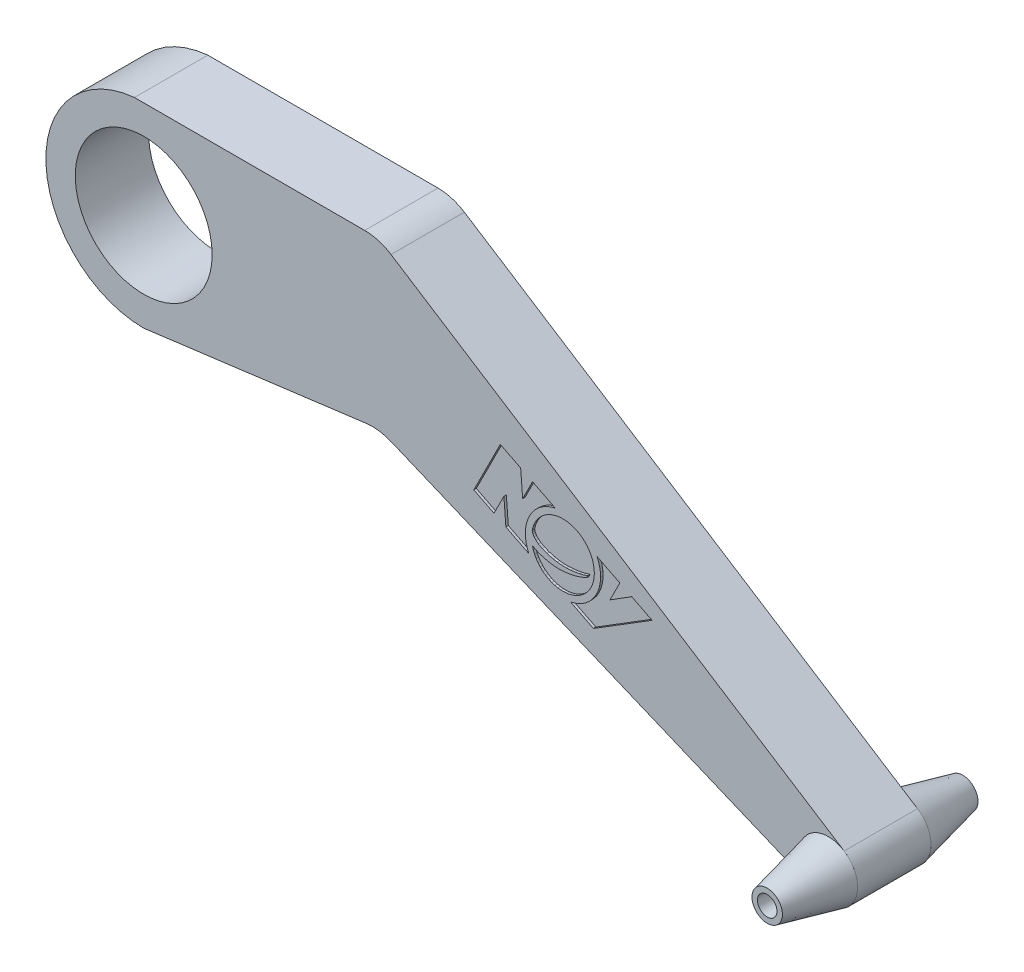
SolidWorks part; units mm, degrees
material "Alumina"
ref_plane "Front Plane" through (0, 0, 0) normal (0, 0, 1) x (1, 0, 0)
ref_plane "Top Plane" through (0, 0, 0) normal (0, 1, 0) x (1, 0, 0)
ref_plane "Right Plane" through (0, 0, 0) normal (1, 0, 0) x (0, 0, -1)
sketch "Sketch1" plane through (0, 0, 0) normal (0, 0, 1) x (1, 0, 0)
  line L1 (-1.8889, 19.9106) -> (45.1848, 19.9106)
  line L5 (50.5757, 18.3331) -> (143.2345, -40.9737)
  line L7 (48.1111, 31.6525) -> (48.1111, -43.2848) construction
  line L10 (140, -52.0272) -> (50.5846, -14.7897)
  line L11 (0, -20) -> (45.4538, -14.1042)
  line L13 (140, -0.7629) -> (140, -46.0272) construction
  circle A0 centre (0, 0) radius 14
  arc A1 (-1.8889, 19.9106) -> (0, -20) centre (0, 0) ccw
  arc A8 (143.2345, -40.9737) -> (140, -52.0272) centre (140, -46.0272) cw
  circle A9 centre (140, -46.0272) radius 2
  arc A11 (50.5757, 18.3331) -> (45.1848, 19.9106) centre (45.1848, 9.9106) ccw
  arc A12 (50.5846, -14.7897) -> (45.4538, -14.1042) centre (46.7401, -24.0212) ccw
  point P12 (48.1111, -13.7596)
  point P20 (48.1111, 19.9106)
  point P22 (140, -46.0272)
  dimension "D1" = 28
  dimension "D2" = 20
  dimension "D3" = 50
  dimension "D4" = 4
  dimension "D6" = 140
  dimension "D7" = 150
  dimension "D5" = 10
  dimension "D9" = 34.0148
  dimension "D8" = 6
  dimension "D10" = 45.4538
  dimension "D11" = 10
extrude "Boss-Extrude1" add sketch "Sketch1" along normal mid plane 15
sketch "Sketch2" plane through (0, 0, 7.5) normal (0, 0, 1) x (1, 0, 0)
  line L0 (0, 0) -> (30.9788, 0) construction
  line L1 (50, 0) -> (-50, 0) construction
  line L2 (15.4894, -1.5) -> (15.4894, 1.5)
  line L3 (15.4894, 1.5) -> (13.9194, 1.5)
  line L4 (15.4894, -1.5) -> (13.9194, -1.5)
  circle A0 centre (0, 0) radius 14 construction
  arc A1 (13.9194, -1.5) -> (13.9194, 1.5) centre (0, 0) ccw
  point P10 (15.4894, 0)
  dimension "D1" = 1.57
  dimension "D2" = 3
extrude "Cut-Extrude1" [suppressed] cut sketch "Sketch2" against normal mid plane 33.14
sketch "Sketch3" [suppressed] plane through (0, 0, 7.5) normal (0, 0, 1) x (1, 0, 0)
  line L0 (0, 33) -> (0, -33) construction
  line L1 (0, -50) -> (0, 50) construction
  line L2 (-6.5, 33) -> (6.5, 33)
  line L3 (6.5, 33) -> (6.5, -33)
  line L4 (6.5, -33) -> (-6.5, -33)
  line L5 (-6.5, -33) -> (-6.5, 33)
  point P10 (0, 33)
  dimension "D1" = 33
  dimension "D2" = 13
  dimension "D3" = 33
extrude "Boss-Extrude2" [suppressed] add sketch "Sketch3" against normal blind 15
sketch "Sketch4" [suppressed] plane through (0, 0, 7.5) normal (0, 0, 1) x (1, 0, 0)
  line L0 (0, 33) -> (0, -33) construction
  line L1 (6.5, 33) -> (-6.5, 33) construction
  line L2 (-6.5, -33) -> (6.5, -33) construction
  line L3 (-7.9109, 0) -> (7.7913, 0) construction
  line L4 (50, 0) -> (-50, 0) construction
  circle A0 centre (0, 0) radius 14
  circle A1 centre (0, 25.4313) radius 4
  circle A2 centre (0, -25.4313) radius 4
  dimension "D1" = 28
  dimension "D2" = 8
  dimension "D3" = 25.4313
extrude "Cut-Extrude2" [suppressed] cut sketch "Sketch4" against normal blind 15
fillet "Fillet1" [suppressed] radius 4
ref_plane "Plane2" through (0, 0, -7.5) normal (0, 0, -1) x (-1, 0, 0)
sketch "Sketch5" plane through (0, 0, -7.5) normal (0, 0, -1) x (-1, 0, 0)
  circle A0 centre (-140, -46.0272) radius 6
extrude "Boss-Extrude3" add sketch "Sketch5" along normal blind 12.5 draft 13 separate body contours A0
sketch "Sketch6" plane through (0, 0, -20) normal (0, 0, -1) x (-1, 0, 0)
  circle A0 centre (-140, -46.0272) radius 2
extrude "Cut-Extrude3" cut sketch "Sketch6" against normal blind 12.5 contours A0
ref_plane "Plane3" through (0, 0, 7.5) normal (0, 0, -1) x (-1, 0, 0)
mirror "Mirror4" about plane through (0, 0, 0) normal (0, 0, 1) of bodies 106
ref_plane "Plane4" through (0, 0, -7.5) normal (0, 0, -1) x (-1, 0, 0)
sketch "Sketch8" plane through (0, 0, -7.5) normal (0, 0, -1) x (-1, 0, 0)
  line L0 (-79.551, -14.2243) -> (-79.2828, -14.8235)
  line L1 (-79.2828, -14.8235) -> (-79.0804, -15.4349)
  line L2 (-79.0804, -15.4349) -> (-78.9422, -16.0541)
  line L3 (-78.9422, -16.0541) -> (-78.8669, -16.6769)
  line L4 (-78.8669, -16.6769) -> (-78.853, -17.299)
  line L5 (-78.853, -17.299) -> (-78.8992, -17.9158)
  line L6 (-78.8992, -17.9158) -> (-79.004, -18.5233)
  line L7 (-79.004, -18.5233) -> (-79.1661, -19.1169)
  line L8 (-79.1661, -19.1169) -> (-79.3839, -19.6924)
  line L9 (-79.3839, -19.6924) -> (-79.6562, -20.2454)
  line L10 (-79.6562, -20.2454) -> (-79.9815, -20.7716)
  line L11 (-79.9815, -20.7716) -> (-80.3583, -21.2667)
  line L12 (-80.3583, -21.2667) -> (-80.7854, -21.7263)
  line L13 (-80.7854, -21.7263) -> (-81.2612, -22.1461)
  line L14 (-81.2612, -22.1461) -> (-81.7843, -22.5217)
  line L15 (-81.7843, -22.5217) -> (-82.3534, -22.8488)
  line L16 (-82.3534, -22.8488) -> (-83.0249, -23.1445)
  line L17 (-83.0249, -23.1445) -> (-83.7111, -23.3581)
  line L18 (-83.7111, -23.3581) -> (-84.4058, -23.4916)
  line L19 (-84.4058, -23.4916) -> (-85.103, -23.547)
  line L20 (-85.103, -23.547) -> (-85.7966, -23.5262)
  line L21 (-85.7966, -23.5262) -> (-86.4805, -23.4313)
  line L22 (-86.4805, -23.4313) -> (-87.1486, -23.2642)
  line L23 (-87.1486, -23.2642) -> (-87.7949, -23.027)
  line L24 (-87.7949, -23.027) -> (-87.1299, -22.7307)
  line L25 (-87.1299, -22.7307) -> (-86.3728, -22.2754)
  line L26 (-86.3728, -22.2754) -> (-85.5204, -21.6356)
  line L27 (-85.5204, -21.6356) -> (-84.5695, -20.7858)
  line L28 (-84.5695, -20.7858) -> (-83.8725, -20.0409)
  line L29 (-83.8725, -20.0409) -> (-83.2548, -19.2361)
  line L30 (-83.2548, -19.2361) -> (-82.7149, -18.3881)
  line L31 (-82.7149, -18.3881) -> (-82.2513, -17.5137)
  line L32 (-82.2513, -17.5137) -> (-81.8625, -16.6296)
  line L33 (-81.8625, -16.6296) -> (-81.5469, -15.7526)
  line L34 (-81.5469, -15.7526) -> (-81.303, -14.8993)
  line L35 (-81.303, -14.8993) -> (-81.1292, -14.0865)
  line L36 (-81.1292, -14.0865) -> (-81.3655, -13.7762)
  line L37 (-81.3655, -13.7762) -> (-81.6354, -14.5442)
  line L38 (-81.6354, -14.5442) -> (-81.967, -15.3373)
  line L39 (-81.967, -15.3373) -> (-82.3578, -16.1402)
  line L40 (-82.3578, -16.1402) -> (-82.8049, -16.9373)
  line L41 (-82.8049, -16.9373) -> (-83.3057, -17.713)
  line L42 (-83.3057, -17.713) -> (-83.8576, -18.4519)
  line L43 (-83.8576, -18.4519) -> (-84.4578, -19.1384)
  line L44 (-84.4578, -19.1384) -> (-85.1037, -19.757)
  line L45 (-85.1037, -19.757) -> (-86.1224, -20.5643)
  line L46 (-86.1224, -20.5643) -> (-87.0136, -21.1285)
  line L47 (-87.0136, -21.1285) -> (-87.7822, -21.4864)
  line L48 (-87.7822, -21.4864) -> (-88.4331, -21.6753)
  line L49 (-88.4331, -21.6753) -> (-88.9714, -21.732)
  line L50 (-88.9714, -21.732) -> (-89.4021, -21.6936)
  line L51 (-89.4021, -21.6936) -> (-89.73, -21.5971)
  line L52 (-89.73, -21.5971) -> (-89.9601, -21.4797)
  line L53 (-89.9601, -21.4797) -> (-90.0224, -21.4349)
  line L54 (-90.0224, -21.4349) -> (-90.5407, -20.7802)
  line L55 (-90.5407, -20.7802) -> (-90.9783, -20.0468)
  line L56 (-90.9783, -20.0468) -> (-91.2464, -19.4476)
  line L57 (-91.2464, -19.4476) -> (-91.4489, -18.8361)
  line L58 (-91.4489, -18.8361) -> (-91.5871, -18.2168)
  line L59 (-91.5871, -18.2168) -> (-91.6625, -17.5939)
  line L60 (-91.6625, -17.5939) -> (-91.6764, -16.9719)
  line L61 (-91.6764, -16.9719) -> (-91.6302, -16.355)
  line L62 (-91.6302, -16.355) -> (-91.5254, -15.7475)
  line L63 (-91.5254, -15.7475) -> (-91.3634, -15.1539)
  line L64 (-91.3634, -15.1539) -> (-91.1455, -14.5784)
  line L65 (-91.1455, -14.5784) -> (-90.8733, -14.0253)
  line L66 (-90.8733, -14.0253) -> (-90.548, -13.4991)
  line L67 (-90.548, -13.4991) -> (-90.1711, -13.004)
  line L68 (-90.1711, -13.004) -> (-89.7441, -12.5444)
  line L69 (-89.7441, -12.5444) -> (-89.2682, -12.1246)
  line L70 (-89.2682, -12.1246) -> (-88.745, -11.7489)
  line L71 (-88.745, -11.7489) -> (-88.1758, -11.4218)
  line L72 (-88.1758, -11.4218) -> (-87.5766, -11.1536)
  line L73 (-87.5766, -11.1536) -> (-86.9653, -10.9512)
  line L74 (-86.9653, -10.9512) -> (-86.346, -10.813)
  line L75 (-86.346, -10.813) -> (-85.7232, -10.7376)
  line L76 (-85.7232, -10.7376) -> (-85.1011, -10.7238)
  line L77 (-85.1011, -10.7238) -> (-84.4842, -10.7699)
  line L78 (-84.4842, -10.7699) -> (-83.8768, -10.8747)
  line L79 (-83.8768, -10.8747) -> (-83.2831, -11.0368)
  line L80 (-83.2831, -11.0368) -> (-82.7076, -11.2546)
  line L81 (-82.7076, -11.2546) -> (-82.1546, -11.5269)
  line L82 (-82.1546, -11.5269) -> (-81.6283, -11.8521)
  line L83 (-81.6283, -11.8521) -> (-81.1332, -12.229)
  line L84 (-81.1332, -12.229) -> (-80.6736, -12.6561)
  line L85 (-80.6736, -12.6561) -> (-80.2538, -13.1319)
  line L86 (-80.2538, -13.1319) -> (-79.8781, -13.6551)
  line L87 (-79.8781, -13.6551) -> (-79.551, -14.2243)
  line L88 (-76.6715, -6.0002) -> (-77.0514, -11.2288)
  line L89 (-77.0514, -11.2288) -> (-79.0881, -7.2315)
  line L90 (-79.0881, -7.2315) -> (-83.73, -9.5967)
  line L91 (-83.73, -9.5967) -> (-82.9103, -9.8114)
  line L92 (-82.9103, -9.8114) -> (-82.1189, -10.1143)
  line L93 (-82.1189, -10.1143) -> (-81.3639, -10.5028)
  line L94 (-81.3639, -10.5028) -> (-80.653, -10.9744)
  line L95 (-80.653, -10.9744) -> (-79.9941, -11.5266)
  line L96 (-79.9941, -11.5266) -> (-79.3951, -12.157)
  line L97 (-79.3951, -12.157) -> (-78.8639, -12.863)
  line L98 (-78.8639, -12.863) -> (-78.4083, -13.6421)
  line L99 (-78.4083, -13.6421) -> (-78.0458, -14.4685)
  line L100 (-78.0458, -14.4685) -> (-77.787, -15.3132)
  line L101 (-77.787, -15.3132) -> (-77.6291, -16.1682)
  line L102 (-77.6291, -16.1682) -> (-77.5696, -17.0258)
  line L103 (-77.5696, -17.0258) -> (-77.6059, -17.8781)
  line L104 (-77.6059, -17.8781) -> (-77.7354, -18.7173)
  line L105 (-77.7354, -18.7173) -> (-77.9556, -19.5354)
  line L106 (-77.9556, -19.5354) -> (-78.2637, -20.3248)
  line L107 (-78.2637, -20.3248) -> (-73.6039, -17.9505)
  line L108 (-73.6039, -17.9505) -> (-72.5101, -3.8799)
  line L109 (-72.5101, -3.8799) -> (-76.6715, -6.0002)
  line L110 (-86.7991, -24.6739) -> (-91.4762, -27.0569)
  line L111 (-91.4762, -27.0569) -> (-95.9297, -24.2911)
  line L112 (-95.9297, -24.2911) -> (-93.893, -28.2884)
  line L113 (-93.893, -28.2884) -> (-98.0097, -30.3859)
  line L114 (-98.0097, -30.3859) -> (-103.476, -19.6578)
  line L115 (-103.476, -19.6578) -> (-99.3243, -17.5424)
  line L116 (-99.3243, -17.5424) -> (-94.8707, -20.3081)
  line L117 (-94.8707, -20.3081) -> (-96.9074, -16.3109)
  line L118 (-96.9074, -16.3109) -> (-92.2653, -13.9456)
  line L119 (-92.2653, -13.9456) -> (-92.5734, -14.735)
  line L120 (-92.5734, -14.735) -> (-92.7935, -15.5533)
  line L121 (-92.7935, -15.5533) -> (-92.9231, -16.3925)
  line L122 (-92.9231, -16.3925) -> (-92.9594, -17.2448)
  line L123 (-92.9594, -17.2448) -> (-92.8999, -18.1025)
  line L124 (-92.8999, -18.1025) -> (-92.742, -18.9576)
  line L125 (-92.742, -18.9576) -> (-92.4831, -19.8023)
  line L126 (-92.4831, -19.8023) -> (-92.1206, -20.6289)
  line L127 (-92.1206, -20.6289) -> (-91.6651, -21.4079)
  line L128 (-91.6651, -21.4079) -> (-91.1339, -22.1138)
  line L129 (-91.1339, -22.1138) -> (-90.5349, -22.7441)
  line L130 (-90.5349, -22.7441) -> (-89.8761, -23.2963)
  line L131 (-89.8761, -23.2963) -> (-89.1652, -23.7678)
  line L132 (-89.1652, -23.7678) -> (-88.4102, -24.1563)
  line L133 (-88.4102, -24.1563) -> (-87.6189, -24.4591)
  line L134 (-87.6189, -24.4591) -> (-86.7991, -24.6739)
extrude "Cut-Extrude4" cut sketch "Sketch8" against normal blind 0.5
sketch "Sketch10" plane through (0, 0, 7.5) normal (0, 0, -1) x (-1, 0, 0)
  line L0 (-90.1816, -7.0169) -> (-80.0322, -27.0533)
  line L1 (-143.2345, -40.9737) -> (-50.5757, 18.3331) construction
  line L2 (-50.5846, -14.7897) -> (-140, -52.0272) construction
  line L7 (-50.5757, 18.3331) -> (-143.2345, -40.9737)
  line L8 (1.8889, 19.9106) -> (-45.1848, 19.9106)
  line L9 (-45.4538, -14.1042) -> (0, -20)
  line L10 (-140, -52.0272) -> (-50.5846, -14.7897)
  line L11 (-50.5757, 18.3331) -> (-90.1816, -7.0169)
  line L12 (1.8889, 19.9106) -> (-45.1848, 19.9106)
  line L13 (-45.4538, -14.1042) -> (0, -20)
  line L14 (-80.0322, -27.0533) -> (-50.5846, -14.7897)
  arc A4 (-143.2345, -40.9737) -> (-140, -52.0272) centre (-140, -46.0272) ccw
  arc A5 (-45.1848, 19.9106) -> (-50.5757, 18.3331) centre (-45.1848, 9.9106) ccw
  arc A6 (0, -20) -> (1.8889, 19.9106) centre (0, 0) ccw
  arc A7 (-45.4538, -14.1042) -> (-50.5846, -14.7897) centre (-46.7401, -24.0212) ccw
  arc A9 (-45.1848, 19.9106) -> (-50.5757, 18.3331) centre (-45.1848, 9.9106) ccw
  arc A10 (0, -20) -> (1.8889, 19.9106) centre (0, 0) ccw
  arc A11 (-45.4538, -14.1042) -> (-50.5846, -14.7897) centre (-46.7401, -24.0212) ccw
  dimension "D1" = 0
ref_axis "Axis1" through (90.1816, -7.0169, 7.5) along (-0.4519, -0.8921, 0)
ref_plane "Plane5" through (74.5954, -37.7862, 0) normal (-0.8921, 0.4519, 0) x (-0.4519, -0.8921, 0)
ref_plane "Plane6" through (0, 0, 8.5) normal (0, 0, -1) x (-1, 0, 0)
sketch "Sketch15" plane through (0, 0, 8.5) normal (0, 0, -1) x (-1, 0, 0)
  line L136 (-78.4365, -19.7446) -> (-78.7484, -20.5325)
  line L137 (-78.2126, -18.9274) -> (-78.4365, -19.7446)
  line L138 (-78.0791, -18.0889) -> (-78.2126, -18.9274)
  line L139 (-78.0387, -17.2368) -> (-78.0791, -18.0889)
  line L140 (-78.0941, -16.379) -> (-78.0387, -17.2368)
  line L141 (-78.248, -15.5232) -> (-78.0941, -16.379)
  line L142 (-78.5028, -14.6773) -> (-78.248, -15.5232)
  line L143 (-78.8613, -13.8492) -> (-78.5028, -14.6773)
  line L144 (-79.3133, -13.0679) -> (-78.8613, -13.8492)
  line L145 (-79.8412, -12.3594) -> (-79.3133, -13.0679)
  line L146 (-80.4372, -11.7262) -> (-79.8412, -12.3594)
  line L147 (-81.0934, -11.1709) -> (-80.4372, -11.7262)
  line L148 (-81.8021, -10.6959) -> (-81.0934, -11.1709)
  line L149 (-82.5553, -10.3039) -> (-81.8021, -10.6959)
  line L150 (-83.3452, -9.9973) -> (-82.5553, -10.3039)
  line L151 (-84.164, -9.7787) -> (-83.3452, -9.9973)
  line L152 (-79.5107, -7.4354) -> (-84.164, -9.7787)
  line L153 (-77.493, -11.4422) -> (-79.5107, -7.4354)
  line L154 (-77.088, -6.2154) -> (-77.493, -11.4422)
  line L155 (-72.9264, -4.1197) -> (-77.088, -6.2154)
  line L156 (-67.511, -14.8736) -> (-72.9264, -4.1197)
  line L157 (-71.6375, -16.9516) -> (-67.511, -14.8736)
  line L158 (-73.6552, -12.9448) -> (-71.6375, -16.9516)
  line L159 (-74.0601, -18.1716) -> (-73.6552, -12.9448)
  line L160 (-78.7484, -20.5325) -> (-74.0601, -18.1716)
  line L161 (-103.9666, -19.7509) -> (-99.7952, -17.6503)
  line L162 (-91.9753, -27.1933) -> (-103.9666, -19.7509)
  line L163 (-87.3044, -24.8411) -> (-91.9753, -27.1933)
  line L164 (-88.1231, -24.6225) -> (-87.3044, -24.8411)
  line L165 (-88.9129, -24.316) -> (-88.1231, -24.6225)
  line L166 (-89.6661, -23.9239) -> (-88.9129, -24.316)
  line L167 (-90.3747, -23.449) -> (-89.6661, -23.9239)
  line L168 (-91.0309, -22.8937) -> (-90.3747, -23.449)
  line L169 (-91.6269, -22.2606) -> (-91.0309, -22.8937)
  line L170 (-92.1547, -21.5521) -> (-91.6269, -22.2606)
  line L171 (-92.6066, -20.771) -> (-92.1547, -21.5521)
  line L172 (-92.9652, -19.9428) -> (-92.6066, -20.771)
  line L173 (-93.2201, -19.0968) -> (-92.9652, -19.9428)
  line L174 (-93.3739, -18.2409) -> (-93.2201, -19.0968)
  line L175 (-93.4294, -17.383) -> (-93.3739, -18.2409)
  line L176 (-93.389, -16.5309) -> (-93.4294, -17.383)
  line L177 (-93.2555, -15.6923) -> (-93.389, -16.5309)
  line L178 (-93.0316, -14.8751) -> (-93.2555, -15.6923)
  line L179 (-92.7197, -14.0872) -> (-93.0316, -14.8751)
  line L180 (-97.3727, -16.4304) -> (-92.7197, -14.0872)
  line L181 (-95.355, -20.4372) -> (-97.3727, -16.4304)
  line L182 (-99.7952, -17.6503) -> (-95.355, -20.4372)
  line L183 (-91.7265, -19.5937) -> (-91.4612, -20.1942)
  line L184 (-91.9261, -18.9813) -> (-91.7265, -19.5937)
  line L185 (-92.0614, -18.3613) -> (-91.9261, -18.9813)
  line L186 (-92.1338, -17.7381) -> (-92.0614, -18.3613)
  line L187 (-92.1447, -17.116) -> (-92.1338, -17.7381)
  line L188 (-92.0956, -16.4993) -> (-92.1447, -17.116)
  line L189 (-91.9879, -15.8923) -> (-92.0956, -16.4993)
  line L190 (-91.8231, -15.2994) -> (-91.9879, -15.8923)
  line L191 (-91.6025, -14.725) -> (-91.8231, -15.2994)
  line L192 (-91.3276, -14.1732) -> (-91.6025, -14.725)
  line L193 (-90.9999, -13.6485) -> (-91.3276, -14.1732)
  line L194 (-90.6207, -13.1553) -> (-90.9999, -13.6485)
  line L195 (-90.1915, -12.6977) -> (-90.6207, -13.1553)
  line L196 (-89.7137, -12.2802) -> (-90.1915, -12.6977)
  line L197 (-89.1888, -11.907) -> (-89.7137, -12.2802)
  line L198 (-88.6181, -11.5826) -> (-89.1888, -11.907)
  line L199 (-88.0176, -11.3173) -> (-88.6181, -11.5826)
  line L200 (-87.4052, -11.1177) -> (-88.0176, -11.3173)
  line L201 (-86.7853, -10.9824) -> (-87.4052, -11.1177)
  line L202 (-86.1621, -10.91) -> (-86.7853, -10.9824)
  line L203 (-85.54, -10.899) -> (-86.1621, -10.91)
  line L204 (-84.9233, -10.9481) -> (-85.54, -10.899)
  line L205 (-84.3163, -11.0558) -> (-84.9233, -10.9481)
  line L206 (-83.7234, -11.2206) -> (-84.3163, -11.0558)
  line L207 (-83.149, -11.4412) -> (-83.7234, -11.2206)
  line L208 (-82.5972, -11.7161) -> (-83.149, -11.4412)
  line L209 (-82.0725, -12.0438) -> (-82.5972, -11.7161)
  line L210 (-81.5792, -12.423) -> (-82.0725, -12.0438)
  line L211 (-81.1217, -12.8523) -> (-81.5792, -12.423)
  line L212 (-80.7041, -13.3301) -> (-81.1217, -12.8523)
  line L213 (-80.3309, -13.8551) -> (-80.7041, -13.3301)
  line L214 (-80.0065, -14.4258) -> (-80.3309, -13.8551)
  line L215 (-79.674, -15.2125) -> (-80.0065, -14.4258)
  line L216 (-79.4528, -16.0176) -> (-79.674, -15.2125)
  line L217 (-79.4536, -16.0943) -> (-79.4528, -16.0176)
  line L218 (-79.495, -16.3494) -> (-79.4536, -16.0943)
  line L219 (-79.6113, -16.6708) -> (-79.495, -16.3494)
  line L220 (-79.8351, -17.0407) -> (-79.6113, -16.6708)
  line L221 (-80.1993, -17.4412) -> (-79.8351, -17.0407)
  line L222 (-80.7366, -17.8543) -> (-80.1993, -17.4412)
  line L223 (-81.4799, -18.2622) -> (-80.7366, -17.8543)
  line L224 (-82.4619, -18.6469) -> (-81.4799, -18.2622)
  line L225 (-83.7155, -18.9906) -> (-82.4619, -18.6469)
  line L226 (-84.5964, -19.1454) -> (-83.7155, -18.9906)
  line L227 (-85.505, -19.2232) -> (-84.5964, -19.1454)
  line L228 (-86.4272, -19.231) -> (-85.505, -19.2232)
  line L229 (-87.3489, -19.1758) -> (-86.4272, -19.231)
  line L230 (-88.256, -19.0647) -> (-87.3489, -19.1758)
  line L231 (-89.1345, -18.9047) -> (-88.256, -19.0647)
  line L232 (-89.9701, -18.7029) -> (-89.1345, -18.9047)
  line L233 (-90.7489, -18.4661) -> (-89.9701, -18.7029)
  line L234 (-90.6386, -18.8403) -> (-90.7489, -18.4661)
  line L235 (-89.8805, -19.181) -> (-90.6386, -18.8403)
  line L236 (-89.0483, -19.4891) -> (-89.8805, -19.181)
  line L237 (-88.1544, -19.7535) -> (-89.0483, -19.4891)
  line L238 (-87.2116, -19.9631) -> (-88.1544, -19.7535)
  line L239 (-86.2324, -20.1067) -> (-87.2116, -19.9631)
  line L240 (-85.2293, -20.1731) -> (-86.2324, -20.1067)
  line L241 (-84.2151, -20.1512) -> (-85.2293, -20.1731)
  line L242 (-83.2021, -20.0299) -> (-84.2151, -20.1512)
  line L243 (-81.9545, -19.766) -> (-83.2021, -20.0299)
  line L244 (-80.9343, -19.4573) -> (-81.9545, -19.766)
  line L245 (-80.1193, -19.1163) -> (-80.9343, -19.4573)
  line L246 (-79.4871, -18.7554) -> (-80.1193, -19.1163)
  line L247 (-79.6782, -19.4168) -> (-79.4871, -18.7554)
  line L248 (-79.9387, -20.0543) -> (-79.6782, -19.4168)
  line L249 (-80.2668, -20.6619) -> (-79.9387, -20.0543)
  line L250 (-80.6604, -21.2333) -> (-80.2668, -20.6619)
  line L251 (-81.1175, -21.7627) -> (-80.6604, -21.2333)
  line L252 (-81.6361, -22.2438) -> (-81.1175, -21.7627)
  line L253 (-82.2142, -22.6706) -> (-81.6361, -22.2438)
  line L254 (-82.8499, -23.0371) -> (-82.2142, -22.6706)
  line L255 (-83.4503, -23.3024) -> (-82.8499, -23.0371)
  line L256 (-84.0627, -23.5019) -> (-83.4503, -23.3024)
  line L257 (-84.6826, -23.6372) -> (-84.0627, -23.5019)
  line L258 (-85.3058, -23.7096) -> (-84.6826, -23.6372)
  line L259 (-85.9278, -23.7205) -> (-85.3058, -23.7096)
  line L260 (-86.5445, -23.6715) -> (-85.9278, -23.7205)
  line L261 (-87.1515, -23.5638) -> (-86.5445, -23.6715)
  line L262 (-87.7443, -23.399) -> (-87.1515, -23.5638)
  line L263 (-88.3188, -23.1784) -> (-87.7443, -23.399)
  line L264 (-88.8705, -22.9036) -> (-88.3188, -23.1784)
  line L265 (-89.3952, -22.5759) -> (-88.8705, -22.9036)
  line L266 (-89.8885, -22.1967) -> (-89.3952, -22.5759)
  line L267 (-90.3461, -21.7675) -> (-89.8885, -22.1967)
  line L268 (-90.7636, -21.2897) -> (-90.3461, -21.7675)
  line L269 (-91.1367, -20.7648) -> (-90.7636, -21.2897)
  line L270 (-91.4612, -20.1942) -> (-91.1367, -20.7648)
extrude "Cut-Extrude9" cut sketch "Sketch15" along normal blind 0.5 from surface contours L136 L160 L159 L158 L157 L156 L155 L154 L153 L152 L151 L150 L149 L148 L147 L146 L145 L144 L143 L142 L141 L140 L139 L138 L137 | L183 L270 L269 L268 L267 L266 L265 L264 L263 L262 L261 L260 L259 L258 L257 L256 L255 L254 L253 L252 L251 L250 L249 L248 L247 L246 L245 L244 L243 L242 L241 L240 L239 L238 L237 L236 L235 L234 L233 L232 L231 L230 L229 L228 L227 L226 L225 L224 L223 L222 L221 | L182 L161 L162 L163 L164 L165 L166 L167 L168 L169 L170 L171 L172 L173 L174 L175 L176 L177 L178 L179 L180 L181 region at (74.9025, -11.8553, 8.5) region at (95.4718, -21.3198, 8.5) region at (85.9375, -17.1357, 8.5) starting at face at (57.3013, -10.6411, 7.5)
